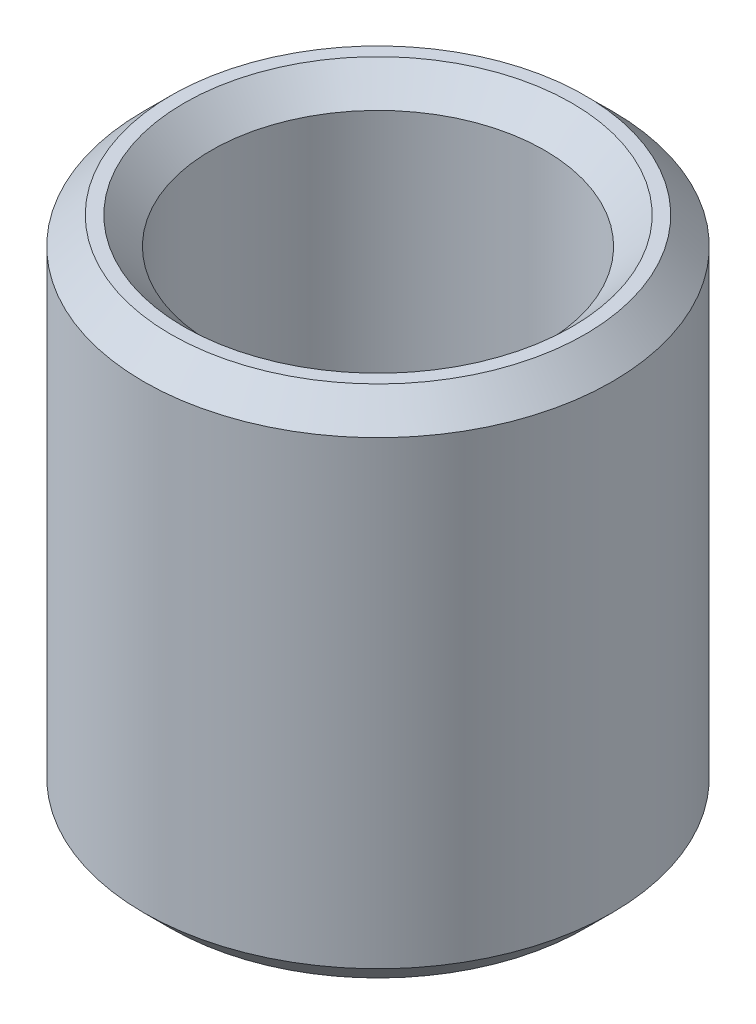
SolidWorks part; units mm, degrees
ref_plane "Front Plane" through (0, 0, 0) normal (0, 0, 1) x (1, 0, 0)
ref_plane "Top Plane" through (0, 0, 0) normal (0, 1, 0) x (1, 0, 0)
ref_plane "Right Plane" through (0, 0, 0) normal (1, 0, 0) x (0, 0, -1)
sketch "Sketch1" plane through (0, 0, 0) normal (0, 1, 0) x (1, 0, 0)
  circle A0 centre (0, 0) radius 10
  dimension "SLEEVE_OD" = 20
extrude "Boss-Extrude1" add sketch "Sketch1" along normal blind 21.9596
sketch "Sketch2" plane through (0, 0, 0) normal (0, 1, 0) x (1, 0, 0)
  circle A0 centre (0, 0) radius 7.1123
  dimension "BORE_D" = 14.2245
extrude "Cut-Extrude1" cut sketch "Sketch2" along normal through all
chamfer "Chamfer1" distance 1.1635 angle 45 4 edges at (0, 21.9596, 7.1123) (0, 0, 7.1123) (0, 0, 10) (0, 21.9596, 10)
